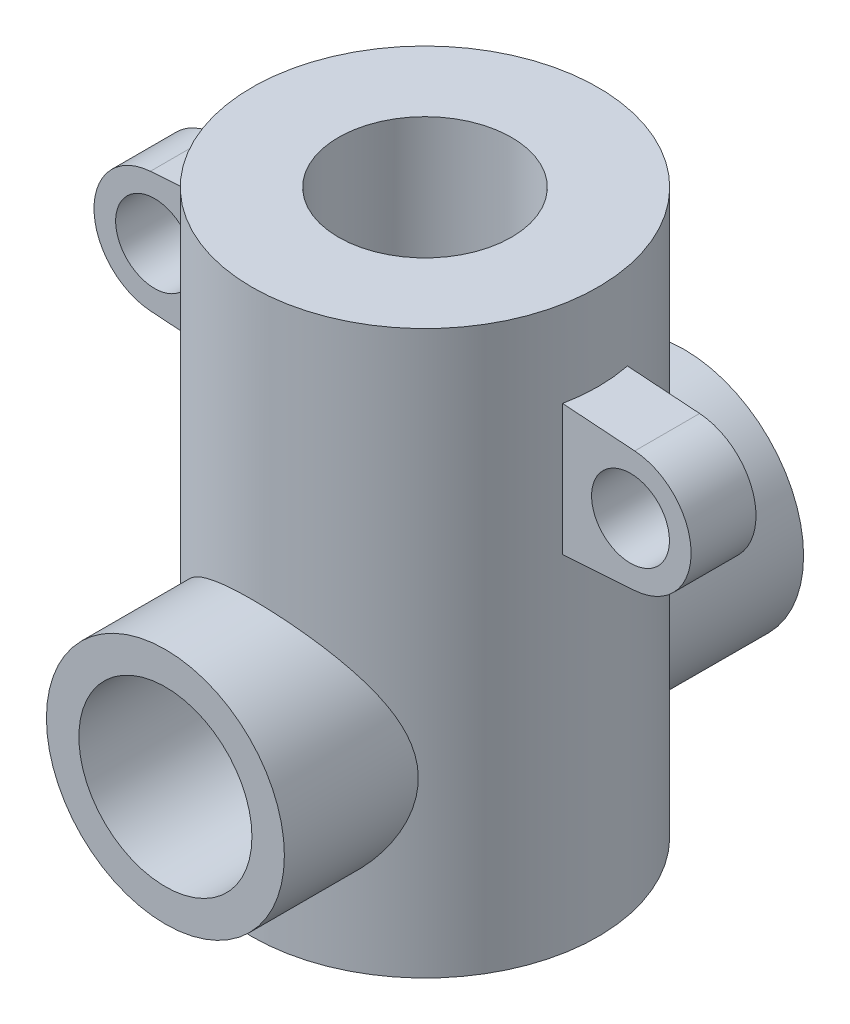
SolidWorks part; units mm, degrees
ref_plane "Front Plane" through (0, 0, 0) normal (0, 0, 1) x (1, 0, 0)
ref_plane "Top Plane" through (0, 0, 0) normal (0, 1, 0) x (1, 0, 0)
ref_plane "Right Plane" through (0, 0, 0) normal (1, 0, 0) x (0, 0, -1)
sketch "Sketch1" plane through (0, 0, 0) normal (0, 1, 0) x (1, 0, 0)
  circle A0 centre (0, 0) radius 40
  circle A1 centre (0, 0) radius 20
  dimension "D1" = 80
  dimension "D2" = 40
extrude "Boss-Extrude1" add sketch "Sketch1" along normal blind 130
sketch "Sketch2" plane through (0, 0, 0) normal (0, 0, 1) x (1, 0, 0)
  line L0 (-40, 0) -> (40, 0) construction
  circle A0 centre (0, 40) radius 27.5
  circle A1 centre (0, 40) radius 20
  dimension "D1" = 55
  dimension "D2" = 40
  dimension "D3" = 40
extrude "Boss-Extrude2" add sketch "Sketch2" along normal mid plane 120
extrude "Cut-Extrude1" cut sketch "Sketch2<2>" against normal through all both and the other way through all contours A1 region at (0, 40, 0)
sketch "Sketch2<2>" plane through (0, 0, 0) normal (0, 0, 1) x (1, 0, 0) same geometry as "Sketch2"
sketch "Sketch3" plane through (0, 0, 0) normal (0, 0, 1) x (1, 0, 0)
  line L0 (-71.7875, 95) -> (71.7875, 95) construction
  line L1 (20, 130) -> (-20, 130) construction
  line L2 (0, 95) -> (0, 118.5925) construction
  line L3 (40, 110.0831) -> (55.9766, 108.9659)
  line L4 (40, 79.9169) -> (55.9766, 81.0341)
  line L5 (40, 0) -> (40, 130) construction
  line L6 (40, 110.0831) -> (25, 111.132)
  line L7 (25, 111.132) -> (25, 78.868)
  line L8 (40, 79.9169) -> (25, 78.868)
  line L9 (-40, 110.0831) -> (-25, 111.132)
  line L10 (-40, 79.9169) -> (-25, 78.868)
  line L11 (-40, 79.9169) -> (-55.9766, 81.0341)
  line L12 (-40, 110.0831) -> (-55.9766, 108.9659)
  line L13 (-25, 111.132) -> (-25, 78.868)
  circle A0 centre (55, 95) radius 9
  circle A1 centre (55, 95) radius 14
  circle A2 centre (-55, 95) radius 9
  circle A3 centre (-55, 95) radius 14
  point P18 (20.434, 76.5832)
  point P20 (16.5734, 76.7394)
  dimension "D2" = 18
  dimension "D3" = 28
  dimension "D1" = 35
  dimension "D4" = 8
  dimension "D5" = 55
  dimension "D6" = 15
extrude "Boss-Extrude3" add sketch "Sketch3" along normal mid plane 15 contours A3 A2 | L12 A3 L11 L10 L13 L9 | A1 A0 | A1 L3 L6 L7 L8 L4 region at (34.8033, 95, 0) region at (64.9494, 104.2779, 0) region at (-34.8033, 95, 0) region at (-45.7221, 104.9494, 0)
sketch "Sketch4" plane through (0, 130, 0) normal (0, 1, 0) x (1, 0, 0)
  circle A0 centre (0, 0) radius 20
extrude "Cut-Extrude2" cut sketch "Sketch4" against normal up to next and the other way through all
sketch "Sketch5" plane through (0, 0, 0) normal (0, -1, 0) x (1, 0, 0)
  circle A0 centre (0, 0) radius 20
extrude "Boss-Extrude4" add sketch "Sketch5" against normal up to surface (12.5 mm away) up to face at (3.3474, 12.7045, 19.7179)
